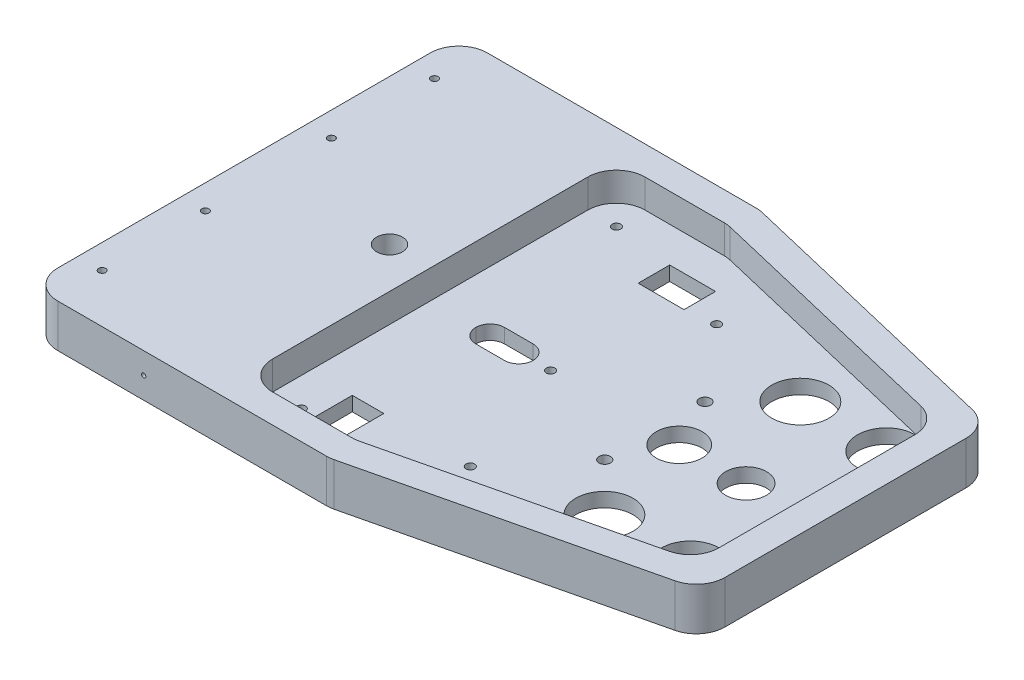
SolidWorks part; units mm, degrees
material "Carvalho"
ref_plane "Plano frontal" through (0, 0, 0) normal (0, 0, 1) x (1, 0, 0)
ref_plane "Plano superior" through (0, 0, 0) normal (0, 1, 0) x (1, 0, 0)
ref_plane "Plano direito" through (0, 0, 0) normal (1, 0, 0) x (0, 0, -1)
sketch "Esboço1" plane through (0, 0, 0) normal (0, 1, 0) x (1, 0, 0)
  line L0 (210, 50) -> (105, 75)
  line L1 (0, -75) -> (105, -75)
  line L2 (0, -75) -> (0, 75)
  line L3 (0, 75) -> (105, 75)
  line L4 (210, -50) -> (210, 50)
  line L7 (105, -75) -> (210, -50)
  line L8 (-14.8259, 0) -> (14.392, 0) construction
  line L9 (0, 21.2472) -> (0, -16.7598) construction
  circle A0 centre (50.8, 0) radius 4.5
  circle A1 centre (175.26, 0) radius 7.14
  circle A2 centre (151.92, 0) radius 8
  circle A3 centre (151.92, 0) radius 8 construction
  circle A4 centre (8.5, -58) radius 1.25
  circle A5 centre (8.5, -22) radius 1.25
  circle A6 centre (8.5, -58) radius 2.5 construction
  circle A7 centre (8.5, -22) radius 2.5 construction
  circle A8 centre (8.5, 22) radius 1.25
  circle A9 centre (8.5, 58) radius 1.25
  point P0 (0, 0)
  dimension "D3" = 9
  dimension "D5" = 14.28
  dimension "D9" = 2.5
  dimension "D1" = 25
  dimension "D2" = 150
  dimension "D4" = 50.8
  dimension "D6" = 210
  dimension "D7" = 175.26
  dimension "D8" = 105
extrude "Ressalto-extrusão1" add sketch "Esboço1" along normal blind 15
sketch "Esboço3" plane through (0, 15, 0) normal (0, 1, 0) x (1, 0, 0)
  line L0 (200, 42.1014) -> (200, -42.1014)
  line L2 (65, -65) -> (65, 65)
  line L6 (210, -50) -> (210, 50) construction
  line L7 (0, 75) -> (0, -75) construction
  line L8 (-22.821, 0) -> (224.4652, 0) construction
  line L9 (65, 65) -> (103.8259, 65)
  line L10 (103.8259, 65) -> (200, 42.1014)
  line L11 (65, -65) -> (103.8259, -65)
  line L12 (103.8259, -65) -> (200, -42.1014)
  line L13 (105, -75) -> (210, -50) construction
  line L14 (0, -75) -> (105, -75) construction
  dimension "D1" = 10
  dimension "D2" = 65
  dimension "D3" = 10
  dimension "D4" = 10
extrude "Corte-extrusão2" cut sketch "Esboço3" against normal blind 10
fillet "Filete1" radius 10 12 edges at (105, 7.5, 75) (0, 7.5, 75) (0, 7.5, -75) (210, 7.5, 50) (105, 7.5, -75) (210, 7.5, -50) (200, 10, 42.1014) (200, 10, -42.1014) (103.8259, 10, 65) (65, 10, 65) (103.8259, 10, -65) (65, 10, -65)
sketch "Esboço5" plane through (0, 0, 0) normal (0, -1, 0) x (1, 0, 0)
  line L0 (175.26, 0) -> (90.92, 0) construction
  line L2 (143.42, 17.5) -> (143.42, -17.5) construction
  line L3 (175.26, 0) -> (101.1849, 0) construction
  line L8 (80.92, -5) -> (100.92, -5)
  line L9 (80.92, -5) -> (80.92, 5)
  line L10 (80.92, 5) -> (100.92, 5)
  line L11 (100.92, -5) -> (100.92, 5)
  line L12 (80.92, -5) -> (100.92, 5) construction
  line L13 (80.92, 5) -> (100.92, -5) construction
  circle A0 centre (143.42, 17.5) radius 2
  circle A1 centre (143.42, -17.5) radius 2
  point P5 (143.42, 0)
  dimension "D6" = 4
  dimension "D1" = 35
  dimension "D2" = 42.5
  dimension "D3" = 20
  dimension "D4" = 31.84
  dimension "D5" = 10
extrude "Corte-extrusão4" cut sketch "Esboço5" against normal through all
fillet "Filete2" radius 5 4 edges at (80.92, 2.5, -5) (80.92, 2.5, 5) (100.92, 2.5, 5) (100.92, 2.5, -5)
sketch "Esboço6" plane through (0, 15, 0) normal (0, 1, 0) x (1, 0, 0)
  line L0 (224.3981, 0) -> (150.0179, 0) construction
  circle A0 centre (190, -34.2028) radius 10
  circle A1 centre (190, 34.2028) radius 10
  circle A2 centre (160, 34.2028) radius 10
  arc A3 (200, 34.2028) -> (192.3162, 43.9309) centre (190, 34.2028) ccw construction
  circle A4 centre (160, -34.2028) radius 10
  arc A5 (200, 34.2028) -> (192.3162, 43.9309) centre (190, 34.2028) ccw construction
  dimension "D3" = 30
extrude "Corte-extrusão5" cut sketch "Esboço6" against normal through all
sketch "Esboço7" plane through (0, 0, 0) normal (0, -1, 0) x (1, 0, 0)
  line L0 (-8.8077, 0) -> (220.236, 0) construction
  line L1 (65, 55) -> (65, -55) construction
  line L3 (90.9, 58.1) -> (79.9, 58.1)
  line L4 (90.9, 58.1) -> (90.9, 42.1)
  line L5 (90.9, 42.1) -> (79.9, 42.1)
  line L6 (79.9, 58.1) -> (79.9, 42.1)
  line L7 (111.9, -41.7) -> (95.9, -41.7)
  line L8 (111.9, -41.7) -> (111.9, -52.7)
  line L9 (111.9, -52.7) -> (95.9, -52.7)
  line L10 (95.9, -41.7) -> (95.9, -52.7)
  line L11 (80.4, 57.6) -> (90.4, 57.6) construction
  line L12 (80.4, 57.6) -> (80.4, 42.6) construction
  line L13 (85.4, 58.1) -> (85.4, 42.1) construction
  line L14 (96.4, -52.2) -> (96.4, -42.2) construction
  line L15 (96.4, -52.2) -> (111.4, -52.2) construction
  circle A3 centre (75, 55) radius 1.5
  circle A5 centre (122, 43) radius 1.5
  circle A6 centre (107, 0) radius 1.5
  circle A7 centre (75, -55) radius 1.5
  circle A8 centre (122, -43) radius 1.5
  dimension "D1" = 55
  dimension "D2" = 3
  dimension "D3" = 43
  dimension "D4" = 47
  dimension "D5" = 10
  dimension "D6" = 32
  dimension "D7" = 11
  dimension "D8" = 0.5
  dimension "D9" = 0.5
  dimension "D10" = 16
  dimension "D11" = 16
  dimension "D12" = 11
  dimension "D13" = 0.5
  dimension "D14" = 0.5
extrude "Corte-extrusão6" cut sketch "Esboço7" against normal through all
sketch "Esboço8" plane through (0, 0, 75) normal (0, 0, 1) x (1, 0, 0)
  line L0 (0, 0) -> (0, 15) construction
  line L1 (40, 15) -> (40, 0) construction
  line L2 (10, 15) -> (103.8259, 15) construction
  line L3 (10, 0) -> (103.8259, 0) construction
  circle A0 centre (40, 7.5) radius 0.75
  dimension "D1" = 1.5
  dimension "D2" = 40
extrude "Corte-extrusão7" cut sketch "Esboço8" against normal through all
